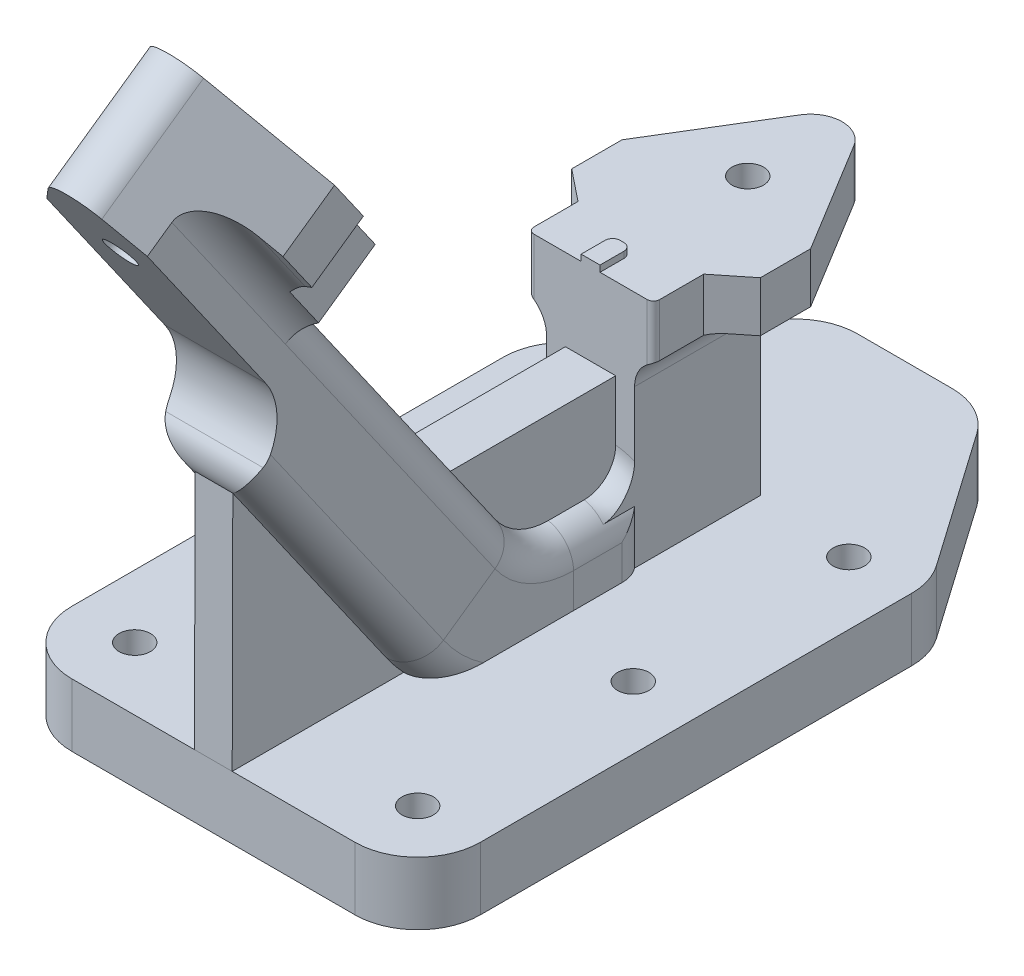
SolidWorks part; units mm, degrees
ref_plane "Front Plane" through (0, 0, 0) normal (0, 0, 1) x (1, 0, 0)
ref_plane "Top Plane" through (0, 0, 0) normal (0, 1, 0) x (1, 0, 0)
ref_plane "Right Plane" through (0, 0, 0) normal (1, 0, 0) x (0, 0, -1)
sketch "Sketch1" plane through (0, 0, 0) normal (0, 1, 0) x (1, 0, 0)
  line L0 (-15, -4) -> (-10, -8)
  line L2 (-15, 4) -> (-15, -4)
  line L3 (-9, -16) -> (9, -16)
  line L4 (15, 4) -> (15, -4)
  line L7 (-10, -8) -> (-10, -15)
  line L8 (0, 9.9023) -> (0, -10.7696) construction
  line L9 (-15, 4) -> (-4.2693, 21.6026)
  line L10 (15, 4) -> (4.2693, 21.6026)
  line L12 (15, -4) -> (10, -8)
  line L13 (10, -8) -> (10, -15)
  arc A0 (4.2693, 21.6026) -> (-4.2693, 21.6026) centre (0, 19) ccw
  arc A1 (10, -15) -> (9, -16) centre (9, -15) cw
  arc A2 (-10, -15) -> (-9, -16) centre (-9, -15) ccw
  point P0 (0, 0)
  point P1 (0, -16)
  point P4 (0, 24)
  point P22 (10, -16)
  point P25 (-10, -16)
  point P26 (-15, 0)
  dimension "D5" = 10
  dimension "D7" = 1
  dimension "D1" = 20
  dimension "D2" = 40
  dimension "D3" = 8
  dimension "D4" = 8
  dimension "D6" = 20
  dimension "D8" = 30
extrude "Boss-Extrude1" add sketch "Sketch1" along normal mid plane 8
sketch "Sketch2" plane through (0, 4, 0) normal (0, 1, 0) x (1, 0, 0)
  line L0 (-9, -16) -> (9, -16) construction
  circle A0 centre (0, 9) radius 2.5
  dimension "D1" = 5
  dimension "D2" = 25
extrude "Cut-Extrude1" cut sketch "Sketch2" against normal mid plane 24
sketch "Sketch3" plane through (0, -4, 0) normal (0, -1, 0) x (1, 0, 0)
  line L0 (-9, 16) -> (9, 16) construction
  line L1 (-7, 16) -> (7, 16)
  line L2 (-7, 16) -> (-7, -4)
  line L3 (-7, -4) -> (-5.5902, -4)
  line L4 (7, 16) -> (7, -4)
  line L5 (5.5902, -4) -> (7, -4)
  arc A0 (5.5902, -4) -> (-5.5902, -4) centre (0, -9) ccw
  point P6 (0, 16)
  dimension "D3" = 15
  dimension "D1" = 14
  dimension "D2" = 20
extrude "Boss-Extrude2" add sketch "Sketch3" along normal blind 40
sketch "Sketch7" plane through (0, 0, 0) normal (1, 0, 0) x (0, 0, -1)
  line L0 (-51, 4) -> (-96.5135, 69) construction
  line L1 (-15, 4) -> (-8, 4) construction
  line L2 (-43.1009, -24.7156) -> (-104.705, 63.2642)
  line L3 (-56.4983, -5.5821) -> (-104.705, 63.2642) construction
  line L4 (-67.7169, 29) -> (12.7663, 29) construction
  line L5 (4, 4) -> (21.6026, 4) construction
  line L6 (-48.3068, 0.1537) -> (-96.5135, 69) construction
  line L7 (-16, 4) -> (-16, -4) construction
  line L8 (-16, -33.244) -> (-26.7179, -33.244)
  arc A0 (-43.1009, -24.7156) -> (-26.7179, -33.244) centre (-26.7179, -13.244) ccw
  dimension "D6" = 20
  dimension "D1" = 125
  dimension "D3" = 25
  dimension "D4" = 40
  dimension "D5" = 35
  dimension "D2" = 10
ref_plane "Plane1" through (0, 63.2642, 104.705) normal (0, 0.8192, 0.5736) x (1, 0, 0)
sketch "Sketch8" plane through (0, 63.2642, 104.705) normal (0, 0.8192, 0.5736) x (1, 0, 0)
  line L5 (0, 17.308) -> (0, 8.5285) construction
  line L6 (-8, 9.7571) -> (8, 9.7571)
  line L8 (-8, 9.7571) -> (-8, -10.2429)
  line L9 (-8, -10.2429) -> (8, -10.2429)
  line L10 (8, 9.7571) -> (8, -10.2429)
  line L11 (-8, 9.7571) -> (8, -10.2429) construction
  line L12 (-8, -10.2429) -> (8, 9.7571) construction
  point P0 (0, -0.2429)
  point P5 (-8, -0.2429)
  dimension "D1" = 16
  dimension "D2" = 20
sweep "Sweep2" add profiles "Sketch8" path "Sketch7"
sketch "Sketch9" plane through (0, -22.7855, 32.5411) normal (0, 0.5736, -0.8192) x (-1, 0, 0)
  line L0 (-18.1274, 102.5962) -> (17.0418, 102.5962) construction
  line L2 (-15, 82.5962) -> (-15, 74.5962)
  line L3 (-10, 62.5962) -> (10, 62.5962)
  line L4 (15, 82.5962) -> (15, 74.5962)
  line L5 (-15, 74.5962) -> (15, 74.5962) construction
  line L7 (0, 4.4759) -> (0, 111.8794) construction
  line L8 (-4.2693, 100.1988) -> (-15, 82.5962)
  line L9 (-15, 74.5962) -> (-10, 70.5962)
  line L10 (-10, 70.5962) -> (-10, 62.5962)
  line L11 (4.2693, 100.1988) -> (15, 82.5962)
  line L12 (15, 74.5962) -> (10, 70.5962)
  line L13 (10, 70.5962) -> (10, 62.5962)
  arc A0 (4.2693, 100.1988) -> (-4.2693, 100.1988) centre (0, 97.5962) ccw
  point P0 (0, 82.5962)
  point P1 (0, 74.5962)
  point P5 (0, 62.5962)
  dimension "D3" = 10
  dimension "D1" = 40
  dimension "D2" = 20
  dimension "D4" = 8
  dimension "D5" = 8
  dimension "D6" = 30
  dimension "D7" = 20
  dimension "D8" = 8
extrude "Boss-Extrude4" add sketch "Sketch9" along normal blind 10 contours L8 L2 L9 L10 L3 L13 L12 L4 L11 A0
sketch "Sketch10" plane through (0, -17.0498, 24.3496) normal (0, 0.5736, -0.8192) x (-1, 0, 0)
  line L0 (-13.1014, 85.7107) -> (-13.1014, 131.1799)
  line L1 (-13.1014, 131.1799) -> (12.4305, 131.1799)
  line L2 (12.4305, 131.1799) -> (12.4305, 86.8113)
  line L9 (-4.2693, 100.1988) -> (-15, 82.5962)
  line L10 (-15, 82.5962) -> (-15, 74.5962)
  line L11 (-15, 74.5962) -> (-10, 70.5962)
  line L12 (-10, 70.5962) -> (-10, 62.5962)
  line L13 (-10, 62.5962) -> (10, 62.5962)
  line L14 (10, 62.5962) -> (10, 70.5962)
  line L15 (10, 70.5962) -> (15, 74.5962)
  line L16 (15, 74.5962) -> (15, 82.5962)
  line L17 (15, 82.5962) -> (4.2693, 100.1988)
  line L18 (-4.2693, 100.1988) -> (-13.1014, 85.7107)
  line L26 (12.4305, 86.8113) -> (4.2693, 100.1988)
  arc A1 (4.2693, 100.1988) -> (-4.2693, 100.1988) centre (0, 97.5962) ccw
  arc A2 (4.2693, 100.1988) -> (-4.2693, 100.1988) centre (0, 97.5962) ccw
  dimension "D1" = 0
extrude "Cut-Extrude2" cut sketch "Sketch10" against normal blind 60
sketch "Sketch11" plane through (0, -17.0498, 24.3496) normal (0, 0.5736, -0.8192) x (-1, 0, 0)
  line L0 (0, 4.4759) -> (0, 111.8794) construction
  line L1 (8, 62.5962) -> (-8, 62.5962) construction
  circle A0 centre (0, 87.5962) radius 2.5
  dimension "D1" = 5
  dimension "D2" = 25
extrude "Cut-Extrude3" cut sketch "Sketch11" against normal blind 60 contours A0
sketch "Sketch12" plane through (0, 0, 0) normal (1, 0, 0) x (0, 0, -1)
  line L0 (-117.126, 43.2343) -> (-99.3804, 55.6599)
  line L1 (-43.1009, -24.7156) -> (-104.705, 63.2642) construction
  line L2 (-99.3804, 55.6599) -> (-75.6738, 21.8033)
  line L3 (-78.1295, 7.876) -> (-85.6618, 2.6019)
  line L4 (-85.6618, 2.6019) -> (-117.126, 43.2343)
  line L5 (-83.1964, 66.9921) -> (-107.7709, 49.7848) construction
  arc A0 (-78.1295, 7.876) -> (-75.6738, 21.8033) centre (-83.8653, 16.0675) ccw
  point P7 (-85.6618, 3.8751)
  dimension "D1" = 20
extrude "Cut-Extrude4" cut sketch "Sketch12" against normal mid plane 60
fillet "Fillet1" radius 5 13 edges at (-8, -40.0698, 40.6825) (-8, -23.487, 21.3589) (-8, -22.3296, 31.4475) (8, -23.487, 21.3589) (8, -22.3296, 31.4475) (8, -40.0698, 40.6825) (-8, -11.427, 64.91) (-8, 4.6856, 51.7766) (8, 4.6856, 51.7766) (8, -11.427, 64.91) (0, 7.7367, 78.3285) (-8, -43.487, 21.3589) (8, -43.487, 21.3589)
sketch "Sketch4" plane through (0, -44, 0) normal (0, -1, 0) x (1, 0, 0)
  line L0 (-30.6915, -8.3135) -> (-15.6915, -29.7358)
  line L1 (-22.5, 76) -> (22.5, 76)
  line L2 (-32.5, 66) -> (-32.5, -2.5778)
  line L3 (-7.5, -34) -> (7.5, -34)
  line L4 (32.5, 66) -> (32.5, -2.5778)
  line L5 (0, 0) -> (0, -33.6545) construction
  line L6 (30.6915, -8.3135) -> (15.6915, -29.7358)
  line L8 (7, 16) -> (-7, 16) construction
  arc A0 (-22.5, 76) -> (-32.5, 66) centre (-22.5, 66) ccw
  arc A1 (32.5, 66) -> (22.5, 76) centre (22.5, 66) ccw
  arc A2 (30.6915, -8.3135) -> (32.5, -2.5778) centre (22.5, -2.5778) ccw
  arc A3 (15.6915, -29.7358) -> (7.5, -34) centre (7.5, -24) cw
  arc A4 (-15.6915, -29.7358) -> (-7.5, -34) centre (-7.5, -24) ccw
  arc A5 (-30.6915, -8.3135) -> (-32.5, -2.5778) centre (-22.5, -2.5778) cw
  circle A6 centre (-22.5, -2.5778) radius 2.5
  circle A7 centre (22.5, -2.5778) radius 2.5
  circle A9 centre (-22.5, 66) radius 2.5
  circle A10 centre (22.5, 66) radius 2.5
  circle A11 centre (-22.5, 31.7111) radius 2.5
  circle A12 centre (22.5, 31.7111) radius 2.5
  point P18 (32.5, -5.7308)
  point P21 (12.7057, -34)
  point P24 (-12.7057, -34)
  point P27 (-32.5, -5.7308)
  point P35 (0, 0)
  point P38 (-32.5, 31.7111)
  point P39 (0, 0)
  point P40 (0, 0)
  dimension "D3" = 20
  dimension "D2" = 10
  dimension "D5" = 215
  dimension "D7" = 60
  dimension "D8" = 5
  dimension "D9" = 5
  dimension "D10" = 5
  dimension "D13" = 10
  dimension "D14" = 5
  dimension "D11" = 5
  dimension "D15" = 5
  dimension "D1" = 65
  dimension "D4" = 110
  dimension "D6" = 15
  dimension "D12" = 10
extrude "Boss-Extrude3" add sketch "Sketch4" against normal blind 10
sketch "Sketch14" plane through (0, 0, 0) normal (1, 0, 0) x (0, 0, -1)
  line L0 (-76, -34) -> (-75.9047, 4.2752)
  line L1 (-51.4914, -30.5907) -> (-75.9047, 4.2752) construction
  arc A0 (-75.8277, 10.1179) -> (-75.9047, 4.2752) centre (-71.809, 7.1431) ccw construction
rib "Rib2" sketch "Sketch14" sketch "Sketch14" thickness 6 extrusion direction parallel to sketch draft on no parameters "D1"=6
sketch "Sketch15" plane through (0, 4, 0) normal (0, 1, 0) x (1, 0, 0)
  line L0 (-9, -16) -> (9, -16) construction
  line L1 (-0.3, -11) -> (0.3, -11)
  line L2 (-1.5, -12.2) -> (-1.5, -16)
  line L3 (-1.5, -16) -> (1.5, -16)
  line L4 (1.5, -12.2) -> (1.5, -16)
  arc A0 (0.3, -11) -> (1.5, -12.2) centre (0.3, -12.2) cw
  arc A1 (-0.3, -11) -> (-1.5, -12.2) centre (-0.3, -12.2) ccw
  point P6 (0, -11)
  point P10 (1.5, -11)
  point P13 (-1.5, -11)
  dimension "D3" = 1.2
  dimension "D1" = 3
  dimension "D2" = 5
extrude "Boss-Extrude5" add sketch "Sketch15" along normal mid plane 2
sketch "Sketch16" plane through (0, -17.0498, 24.3496) normal (0, 0.5736, -0.8192) x (-1, 0, 0)
  line L0 (3, 62.5962) -> (-3, 62.5962) construction
  line L1 (-0.3, 67.5962) -> (0.3, 67.5962)
  line L2 (-1.5, 66.3962) -> (-1.5, 62.5962)
  line L3 (-1.5, 62.5962) -> (1.5, 62.5962)
  line L4 (1.5, 66.3962) -> (1.5, 62.5962)
  arc A0 (0.3, 67.5962) -> (1.5, 66.3962) centre (0.3, 66.3962) cw
  arc A1 (-0.3, 67.5962) -> (-1.5, 66.3962) centre (-0.3, 66.3962) ccw
  point P6 (0, 67.5962)
  point P10 (1.5, 67.5962)
  point P13 (-1.5, 67.5962)
  dimension "D3" = 1.2
  dimension "D1" = 3
  dimension "D2" = 5
extrude "Boss-Extrude6" add sketch "Sketch16" along normal mid plane 2
fillet "Fillet2" radius 5 5 edges at (5.2361, -24.0148, 16) (-5.2361, -24.0148, 16) (0, -23.487, 16) (8, 41.3848, 77.4737) (-8, 41.3848, 77.4737)
fillet "Fillet3" radius 5 2 edges at (7, -4, 6) (-7, -4, 6)
sketch "Sketch17" plane through (0, 0, 0) normal (1, 0, 0) x (0, 0, -1)
  line L0 (-16, -9) -> (-42.1939, -9)
  line L1 (-68.4448, 28.4903) -> (-35.1084, -19.1191) construction
rib "Rib3" sketch "Sketch17" sketch "Sketch17" thickness 8 extrusion direction parallel to sketch draft on no parameters "D1"=8
fillet "Fillet4" radius 5 2 edges at (-8, -31.2435, 16) (8, -31.2435, 16)
